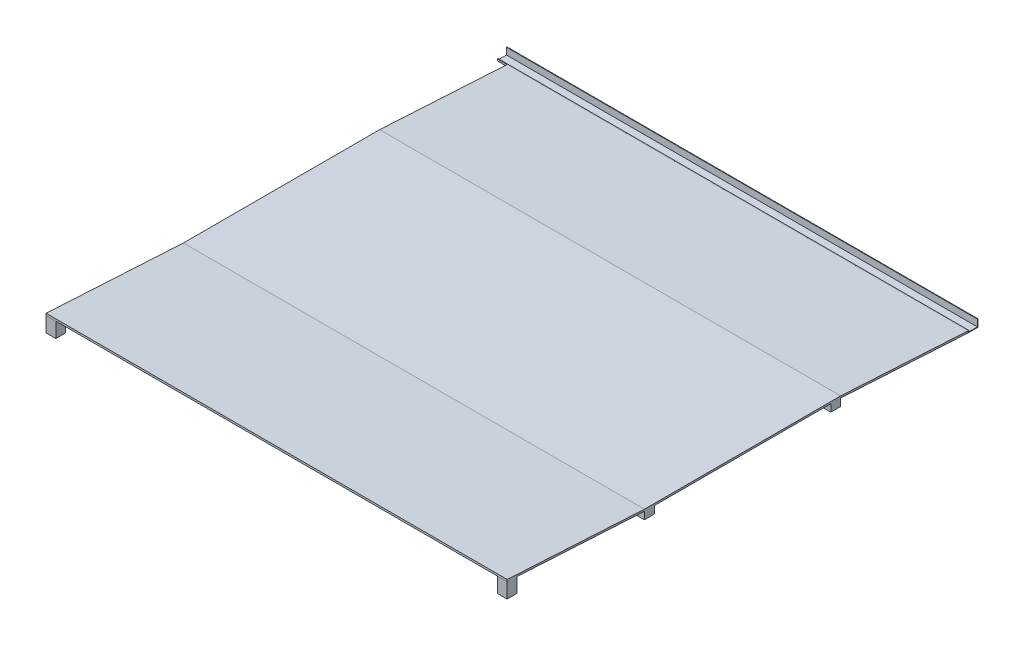
SolidWorks part; units mm, degrees
material "Pine"
ref_plane "Front" through (0, 0, 0) normal (0, 0, 1) x (1, 0, 0)
ref_plane "Top" through (0, 0, 0) normal (0, 1, 0) x (1, 0, 0)
ref_plane "Right" through (0, 0, 0) normal (1, 0, 0) x (0, 0, -1)
sketch "Sketch1" plane through (0, 0, 0) normal (0, 1, 0) x (1, 0, 0)
  line L1 (-2438.4, 2438.4) -> (2438.4, 2438.4) construction
  line L2 (-2438.4, 2438.4) -> (-2438.4, -2438.4) construction
  line L3 (-2438.4, -2438.4) -> (2438.4, -2438.4) construction
  line L4 (2438.4, 2438.4) -> (2438.4, -2438.4) construction
  line L5 (-2438.4, 2438.4) -> (2438.4, -2438.4) construction
  line L6 (-2438.4, -2438.4) -> (2438.4, 2438.4) construction
  point P0 (0, 0)
  dimension "D1" = 4876.8
  dimension "D2" = 4876.8
ref_plane "Plane1" through (0, 0, -2438.4) normal (0, 0, 1) x (1, 0, 0)
ref_plane "Plane2" through (0, 0, 2438.4) normal (0, 0, 1) x (1, 0, 0)
ref_plane "Plane3" through (-2438.4, 0, 0) normal (-1, 0, 0) x (0, 0, 1)
ref_plane "Plane4" through (2438.4, 0, 0) normal (-1, 0, 0) x (0, 0, 1)
sketch "Sketch2" plane through (2438.4, 0, 0) normal (-1, 0, 0) x (0, 0, 1)
  line L0 (-2336.8, 0) -> (-1016, 76.2)
  line L1 (-2438.4, 0) -> (2438.4, 0) construction
  line L2 (-1016, 76.2) -> (1016, 76.2)
  line L3 (1016, 76.2) -> (2438.4, 156.7132)
  line L4 (2438.4, -2486.66) -> (2438.4, 2486.66) construction
  line L5 (2438.4, 0) -> (-2438.4, 0) construction
  line L6 (0, 0) -> (0, 76.2) construction
  line L7 (-2438.4, -2486.66) -> (-2438.4, 2486.66) construction
  dimension "D1" = 76.2
  dimension "D2" = 2032
  dimension "D3" = 3.24
  dimension "D4" = 101.6
extrude "Extrude-Thin1" add sketch "Sketch2" along normal blind 4775.2 thin thin type one direction reverse wall 19.05
sketch "Sketch3" plane through (0, 0, 0) normal (0, 1, 0) x (1, 0, 0)
  line L1 (2438.4, -2438.4) -> (2336.8, -2438.4)
  line L2 (2438.4, -2438.4) -> (2438.4, -2336.8)
  line L3 (2438.4, -2336.8) -> (2336.8, -2336.8)
  line L4 (2336.8, -2438.4) -> (2336.8, -2336.8)
  line L5 (-2336.8, -2438.4) -> (-2235.2, -2438.4)
  line L6 (-2336.8, -2438.4) -> (-2336.8, -2336.8)
  line L7 (-2336.8, -2336.8) -> (-2235.2, -2336.8)
  line L8 (-2235.2, -2438.4) -> (-2235.2, -2336.8)
  line L9 (-2336.8, -1016) -> (-2235.2, -1016)
  line L10 (-2336.8, -1016) -> (-2336.8, -914.4)
  line L11 (-2336.8, -914.4) -> (-2235.2, -914.4)
  line L12 (-2235.2, -1016) -> (-2235.2, -914.4)
  line L13 (-2336.8, 1016) -> (-2235.2, 1016)
  line L14 (-2336.8, 1016) -> (-2336.8, 914.4)
  line L15 (-2336.8, 914.4) -> (-2235.2, 914.4)
  line L16 (-2235.2, 1016) -> (-2235.2, 914.4)
  line L17 (2438.4, 1016) -> (2336.8, 1016)
  line L18 (2438.4, 1016) -> (2438.4, 914.4)
  line L19 (2438.4, 914.4) -> (2336.8, 914.4)
  line L20 (2336.8, 1016) -> (2336.8, 914.4)
  line L21 (2438.4, -1016) -> (2336.8, -1016)
  line L22 (2438.4, -1016) -> (2438.4, -914.4)
  line L23 (2438.4, -914.4) -> (2336.8, -914.4)
  line L24 (2336.8, -1016) -> (2336.8, -914.4)
  dimension "D1" = 101.6
extrude "Boss-Extrude1" add sketch "Sketch3" along normal up to surface (76.2 mm away) up to face at (50.8, 76.2, 0)
sketch "Sketch4" plane through (0, 76.2, 0) normal (0, 1, 0) x (1, 0, 0)
  line L4 (2336.8, -2438.4) -> (2438.4, -2438.4)
  line L5 (2438.4, -2438.4) -> (2438.4, -2336.8)
  line L6 (2438.4, -2336.8) -> (2336.8, -2336.8)
  line L7 (2336.8, -2336.8) -> (2336.8, -2438.4)
  line L8 (2336.8, -2438.4) -> (2438.4, -2438.4)
  line L9 (2438.4, -2438.4) -> (2438.4, -2336.8)
  line L10 (2438.4, -2336.8) -> (2336.8, -2336.8)
  line L11 (2336.8, -2336.8) -> (2336.8, -2438.4)
  line L12 (-2235.2, -2336.8) -> (-2336.8, -2336.8)
  line L13 (-2336.8, -2336.8) -> (-2336.8, -2438.4)
  line L14 (-2336.8, -2438.4) -> (-2235.2, -2438.4)
  line L15 (-2235.2, -2438.4) -> (-2235.2, -2336.8)
  line L16 (-2235.2, -2336.8) -> (-2336.8, -2336.8)
  line L17 (-2336.8, -2336.8) -> (-2336.8, -2438.4)
  line L18 (-2336.8, -2438.4) -> (-2235.2, -2438.4)
  line L19 (-2235.2, -2438.4) -> (-2235.2, -2336.8)
  dimension "D1" = 0
  dimension "D2" = 0
extrude "Boss-Extrude2" add sketch "Sketch4" along normal up to surface (74.7623 mm away) up to face at (50.8, 103.0377, 1490.1333)
sketch "Sketch5" plane through (-2438.4, 0, 0) normal (-1, 0, 0) x (0, 0, 1)
  line L0 (-2438.4, 76.2) -> (-2438.4, 0)
  line L1 (-2438.4, -2486.66) -> (-2438.4, 2486.66) construction
  line L2 (2438.4, 0) -> (-2438.4, 0) construction
  line L3 (-2438.4, 0) -> (-2337.8972, 0)
  line L4 (-2337.8972, 0) -> (-2337.8972, 19.05)
  line L5 (-2337.8972, 19.05) -> (-2344.2472, 19.05)
  line L6 (-2344.2472, 19.05) -> (-2344.2472, 6.35)
  line L7 (-2344.2472, 6.35) -> (-2432.05, 6.35)
  line L8 (-2432.05, 6.35) -> (-2432.05, 76.2)
  line L9 (-2432.05, 76.2) -> (-2438.4, 76.2)
  line L10 (-2344.2472, 6.35) -> (-2344.2472, 0) construction
  dimension "D1" = 6.35
  dimension "D2" = 76.2
  dimension "D3" = 12.7
extrude "Boss-Extrude3" add sketch "Sketch5" against normal up to surface (4876.8 mm away) separate body up to face at (2438.4, 58.6898, 430.114)
